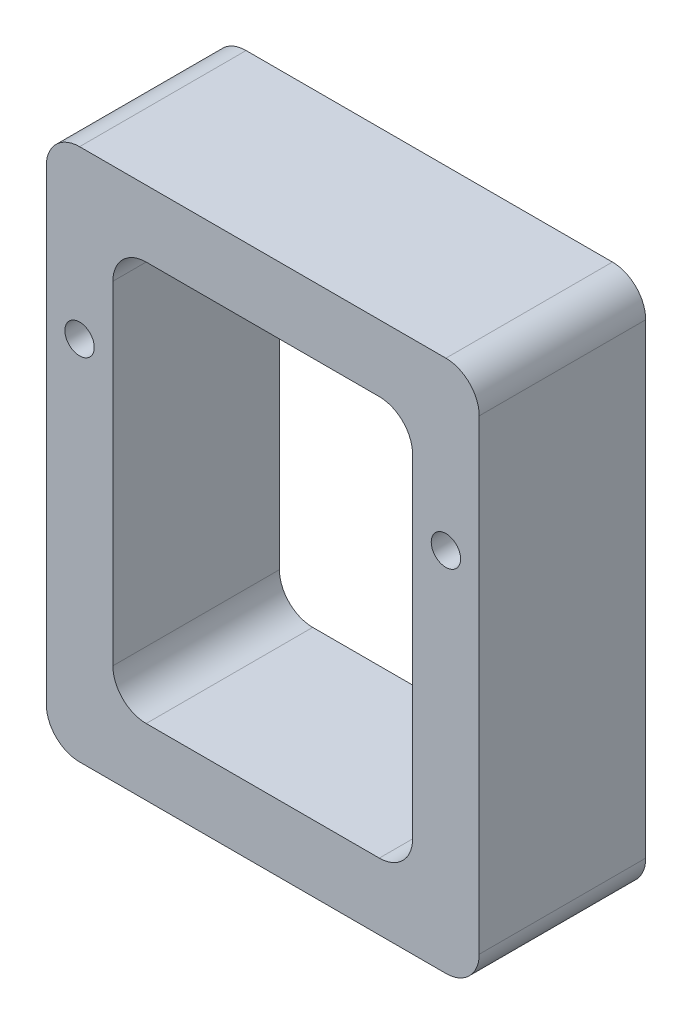
SolidWorks part; units mm, degrees
material "Pink Foam"
ref_plane "Front Plane" through (0, 0, 0) normal (0, 0, 1) x (1, 0, 0)
ref_plane "Top Plane" through (0, 0, 0) normal (0, 1, 0) x (1, 0, 0)
ref_plane "Right Plane" through (0, 0, 0) normal (1, 0, 0) x (0, 0, -1)
sketch "Sketch1" plane through (0, 0, 0) normal (0, 0, 1) x (1, 0, 0)
  line L0 (-114.3, -127) -> (-114.3, 127)
  line L1 (-139.7, -203.2) -> (139.7, -203.2)
  line L2 (-165.1, -177.8) -> (-165.1, 177.8)
  line L3 (-139.7, 203.2) -> (139.7, 203.2)
  line L4 (165.1, -177.8) -> (165.1, 177.8)
  line L5 (-165.1, -203.2) -> (165.1, 203.2) construction
  line L6 (-165.1, 203.2) -> (165.1, -203.2) construction
  line L7 (-88.9, 152.4) -> (88.9, 152.4)
  line L8 (114.3, -127) -> (114.3, 127)
  line L9 (-88.9, -152.4) -> (88.9, -152.4)
  line L10 (114.3, -152.4) -> (114.3, 152.4) construction
  line L11 (-114.3, -152.4) -> (114.3, -152.4) construction
  line L12 (-114.3, 152.4) -> (114.3, 152.4) construction
  line L13 (-114.3, -152.4) -> (-114.3, 152.4) construction
  line L14 (-165.1, -203.2) -> (165.1, -203.2) construction
  line L15 (-165.1, -203.2) -> (-165.1, 203.2) construction
  line L16 (165.1, -203.2) -> (165.1, 203.2) construction
  line L17 (-165.1, 203.2) -> (165.1, 203.2) construction
  line L18 (0, 0) -> (0, 152.4) construction
  line L19 (-114.3, 76.2) -> (-139.7, 76.2) construction
  line L20 (-139.7, 76.2) -> (-165.1, 76.2) construction
  line L21 (114.3, 76.2) -> (139.7, 76.2) construction
  line L22 (139.7, 76.2) -> (165.1, 76.2) construction
  arc A0 (114.3, -127) -> (88.9, -152.4) centre (88.9, -127) cw
  arc A1 (88.9, 152.4) -> (114.3, 127) centre (88.9, 127) cw
  arc A2 (-114.3, 127) -> (-88.9, 152.4) centre (-88.9, 127) cw
  arc A3 (-114.3, -127) -> (-88.9, -152.4) centre (-88.9, -127) ccw
  arc A4 (-139.7, -203.2) -> (-165.1, -177.8) centre (-139.7, -177.8) cw
  arc A5 (139.7, -203.2) -> (165.1, -177.8) centre (139.7, -177.8) ccw
  arc A6 (139.7, 203.2) -> (165.1, 177.8) centre (139.7, 177.8) cw
  arc A7 (-165.1, 177.8) -> (-139.7, 203.2) centre (-139.7, 177.8) cw
  circle A8 centre (-139.7, 76.2) radius 11.2
  circle A9 centre (139.7, 76.2) radius 11.2
  point P0 (0, 0)
  point P39 (0, 0)
  dimension "D4" = 25.4
  dimension "D5" = 22.4
  dimension "D1" = 279.4
  dimension "D2" = 406.4
  dimension "D6" = 76.2
  dimension "D3" = 50.8
extrude "Boss-Extrude1" add sketch "Sketch1" along normal blind 127
